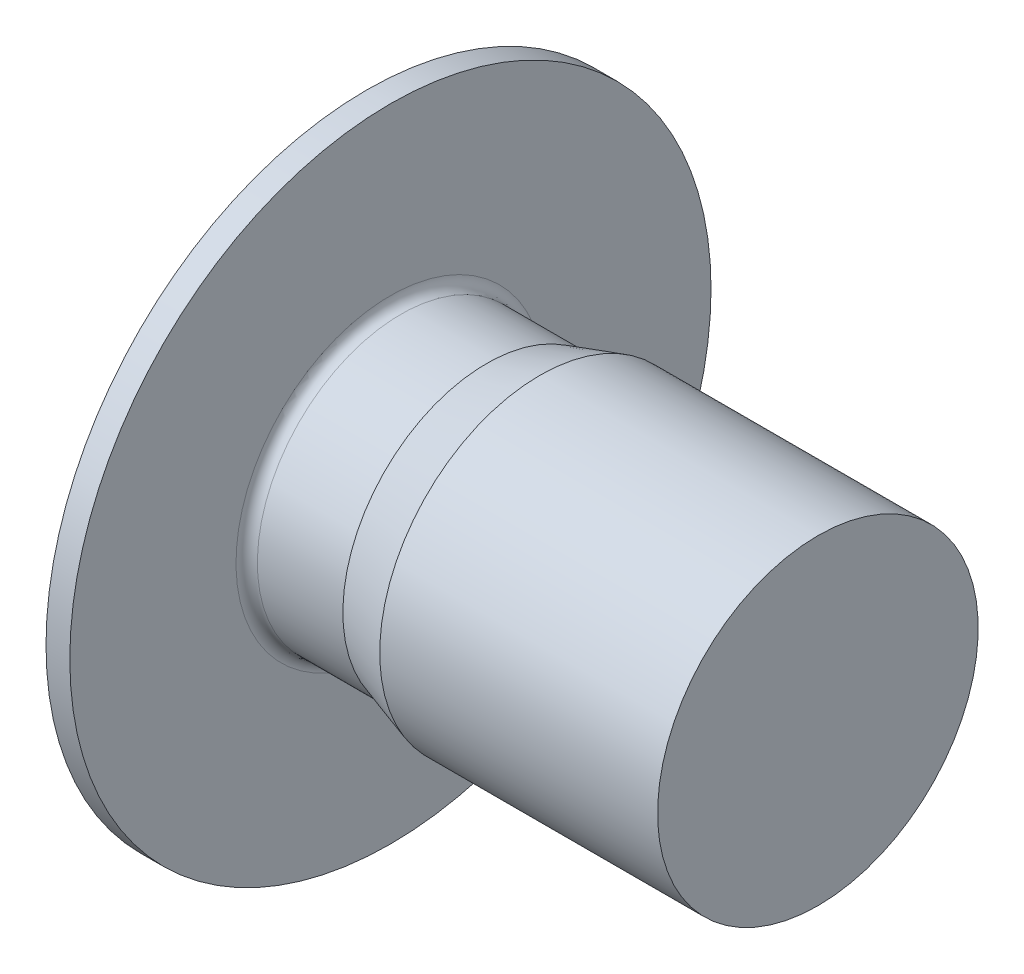
SolidWorks part; units mm, degrees
material "SCM435"
ref_plane "Front Plane" through (0, 0, 0) normal (0, 0, 1) x (1, 0, 0)
ref_plane "Top Plane" through (0, 0, 0) normal (0, 1, 0) x (1, 0, 0)
ref_plane "Right Plane" through (0, 0, 0) normal (1, 0, 0) x (0, 0, -1)
sketch "Sketch1" plane through (0, 0, 0) normal (0, 0, 1) x (1, 0, 0)
  line L0 (-0.8, 0) -> (4, 0) construction
  line L1 (-0.8, 0) -> (-0.8, 2)
  line L2 (-0.2226, 3) -> (0, 3)
  line L3 (0, 3) -> (0, 1.345)
  line L4 (1.4, 1.5) -> (4, 1.5)
  line L5 (4, 1.5) -> (4, 0)
  line L6 (4, 0) -> (-0.8, 0)
  line L7 (1.4, 1.5) -> (0.9, 1.345)
  line L8 (0.9, 1.345) -> (0, 1.345)
  line L9 (-0.2226, 3) -> (-0.8, 2)
  line L10 (-0.8, 0) -> (4, 0) construction
  dimension "A" = 6
  dimension "M" = 3
  dimension "L" = 4
  dimension "MSM_1" = 4
  dimension "E_s" = 1.4
  dimension "E" = 0.8
  dimension "FIX_1" = 30
  dimension "MSM_2" = 2.69
  dimension "MSM_3" = 0.5
revolve "Revolve1" add sketch "Sketch1" angle 360 about L0
cosmetic thread "Thread1" parameters "ATL_1"=2.6, "ATD"=2.459
fillet "Fillet1" radius 0.1 1 edges at (0, -1.345, 0)
sketch "Sketch2" plane through (-0.8, 0, 0) normal (-1, 0, 0) x (0, 0, 1)
  line L1 (0, 0.866) -> (-0.75, 0.433)
  line L2 (-0.75, 0.433) -> (-0.75, -0.433)
  line L3 (-0.75, -0.433) -> (0, -0.866)
  line L4 (0, -0.866) -> (0.75, -0.433)
  line L5 (0.75, -0.433) -> (0.75, 0.433)
  line L6 (0.75, 0.433) -> (0, 0.866)
  circle A0 centre (0, 0) radius 0.75 construction
  dimension "B" = 1.5
extrude "Cut-Extrude1" cut sketch "Sketch2" against normal blind 2
sketch "Sketch3" plane through (0, 0, 0) normal (0, 0, 1) x (1, 0, 0)
  line L0 (1.2, 0) -> (1.6506, 0) construction
  line L1 (1.2, 0) -> (1.2, 0.75)
  line L2 (1.2, 0.75) -> (1.6506, 0)
  line L3 (1.6506, 0) -> (1.2, 0)
  line L5 (1.2, 0.433) -> (1.2, -0.433) construction
  dimension "FIX_3" = 59
  dimension "B" = 1.5
revolve "Cut-Revolve1" cut sketch "Sketch3" angle 360 about L0
equation "\"ATL_1@Thread1\" = \"L@Sketch1\" - \"E_s@Sketch1\""
